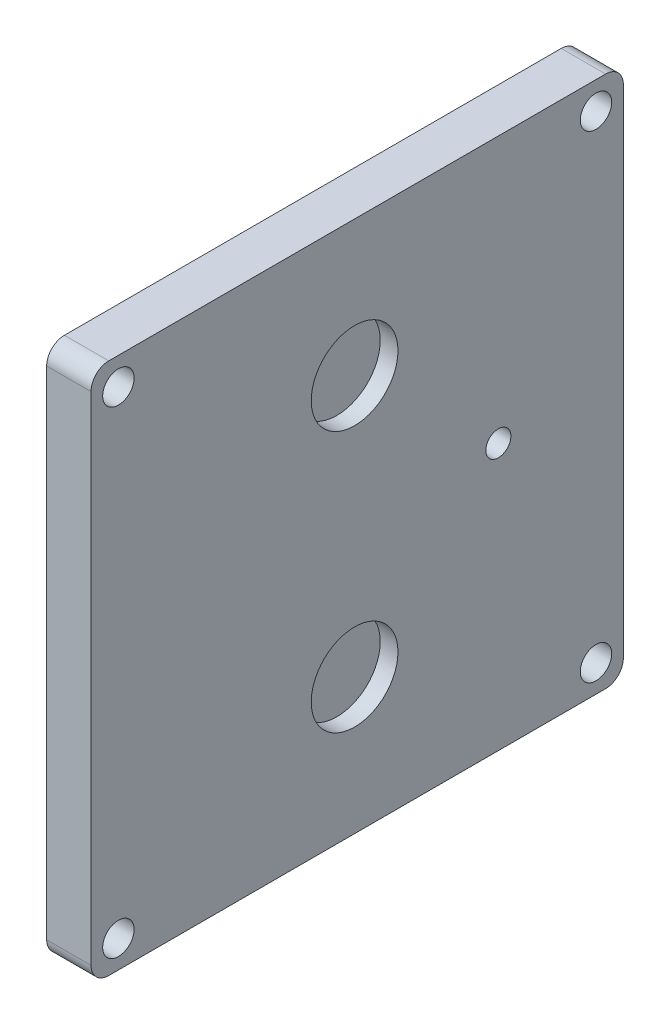
SolidWorks part; units mm, degrees
ref_plane "Front Plane" through (0, 0, 0) normal (0, 0, 1) x (1, 0, 0)
ref_plane "Top Plane" through (0, 0, 0) normal (0, 1, 0) x (1, 0, 0)
ref_plane "Right Plane" through (0, 0, 0) normal (1, 0, 0) x (0, 0, -1)
sketch "Sketch2" plane through (0, 0, 0) normal (1, 0, 0) x (0, 0, -1)
  line L1 (-35.56, -38.1) -> (35.56, -38.1)
  line L2 (-38.1, -35.56) -> (-38.1, 35.56)
  line L3 (-35.56, 38.1) -> (35.56, 38.1)
  line L4 (38.1, -35.56) -> (38.1, 35.56)
  line L5 (-38.1, -38.1) -> (38.1, 38.1) construction
  line L6 (-38.1, 38.1) -> (38.1, -38.1) construction
  arc A0 (-35.56, -38.1) -> (-38.1, -35.56) centre (-35.56, -35.56) cw
  arc A1 (35.56, -38.1) -> (38.1, -35.56) centre (35.56, -35.56) ccw
  arc A2 (35.56, 38.1) -> (38.1, 35.56) centre (35.56, 35.56) cw
  arc A3 (-38.1, 35.56) -> (-35.56, 38.1) centre (-35.56, 35.56) cw
  point P0 (0, 0)
  dimension "D3" = 2.54
  dimension "D1" = 76.2
  dimension "D2" = 76.2
extrude "Boss-Extrude1" add sketch "Sketch2" along normal blind 6.35
sketch "Sketch3" plane through (6.35, 0, 0) normal (1, 0, 0) x (0, 0, -1)
  line L0 (0, 38.1) -> (0, -38.1) construction
  line L1 (35.56, 38.1) -> (-35.56, 38.1) construction
  line L2 (-35.56, -38.1) -> (35.56, -38.1) construction
  line L3 (38.1, 0) -> (-38.1, 0) construction
  line L4 (38.1, -35.56) -> (38.1, 35.56) construction
  line L5 (-38.1, 35.56) -> (-38.1, -35.56) construction
  line L6 (-38.1, 0) -> (37.3561, 37.3561) construction
  line L7 (-38.1, 0) -> (37.3561, -37.3561) construction
  arc A0 (38.1, 35.56) -> (35.56, 38.1) centre (35.56, 35.56) ccw construction
  arc A1 (35.56, -38.1) -> (38.1, -35.56) centre (35.56, -35.56) ccw construction
  circle A2 centre (-0.372, -18.678) radius 6.21
  circle A3 centre (-0.372, 18.678) radius 6.21
  dimension "D1" = 12.42
  dimension "D2" = 12.42
sketch "Sketch6" plane through (6.35, 0, 0) normal (1, 0, 0) x (0, 0, -1)
  line L0 (38.1, 0) -> (-38.1, 0) construction
  circle A0 centre (20.2063, 0) radius 1.778
extrude "Cut-Extrude1" cut sketch "Sketch6" against normal through all
sketch "Sketch14" plane through (6.35, 0, 0) normal (1, 0, 0) x (0, 0, -1)
extrude "Cut-Extrude5" cut sketch "Sketch3" against normal blind 2.54 contours A2 | A3
sketch "Sketch16" plane through (6.35, 0, 0) normal (1, 0, 0) x (0, 0, -1)
  circle A0 centre (20.2063, 0) radius 1.778
sketch "Sketch17" plane through (0, 0, 0) normal (-1, 0, 0) x (0, 0, 1)
  line L6 (-31.75, -31.75) -> (31.75, -31.75)
  line L7 (-31.75, -31.75) -> (-31.75, 31.75)
  line L11 (-31.75, 31.75) -> (31.75, 31.75)
  line L12 (31.75, -31.75) -> (31.75, 31.75)
  line L13 (-31.75, -31.75) -> (31.75, 31.75) construction
  line L14 (-31.75, 31.75) -> (31.75, -31.75) construction
  point P0 (0, 0)
  point P1 (0, 0)
extrude "Boss-Extrude2" add sketch "Sketch17" along normal blind 2.54
fillet "Fillet1" radius 2.54 4 edges at (-1.27, -31.75, 31.75) (-1.27, -31.75, -31.75) (-1.27, 31.75, -31.75) (-1.27, 31.75, 31.75)
sketch "Sketch18" plane through (-2.54, 0, 0) normal (-1, 0, 0) x (0, 0, 1)
  circle A0 centre (-20.2063, 0) radius 1.7965
extrude "Cut-Extrude6" cut sketch "Sketch18" against normal through all
sketch "Sketch21" plane through (-2.54, 0, 0) normal (-1, 0, 0) x (0, 0, 1)
  line L0 (-34.1811, 34.1811) -> (-34.1811, -34.1811) construction
  line L1 (-34.1811, -34.1811) -> (34.1811, -34.1811) construction
  line L2 (31.0061, 31.0061) -> (37.3561, 37.3561) construction
  line L3 (-31.0061, 31.0061) -> (-37.3561, 37.3561) construction
  line L4 (31.0061, -31.0061) -> (37.3561, -37.3561) construction
  line L5 (-31.0061, -31.0061) -> (-37.3561, -37.3561) construction
  line L6 (34.1811, -34.1811) -> (34.1811, 34.1811) construction
  line L7 (34.1811, 34.1811) -> (-34.1811, 34.1811) construction
  arc A0 (-35.56, 38.1) -> (-38.1, 35.56) centre (-35.56, 35.56) ccw construction
  arc A1 (35.56, -38.1) -> (38.1, -35.56) centre (35.56, -35.56) ccw construction
  arc A2 (-38.1, -35.56) -> (-35.56, -38.1) centre (-35.56, -35.56) ccw construction
  arc A3 (38.1, 35.56) -> (35.56, 38.1) centre (35.56, 35.56) ccw construction
  arc A4 (31.75, 29.21) -> (29.21, 31.75) centre (29.21, 29.21) ccw construction
  arc A5 (-29.21, 31.75) -> (-31.75, 29.21) centre (-29.21, 29.21) ccw construction
  arc A6 (-31.75, -29.21) -> (-29.21, -31.75) centre (-29.21, -29.21) ccw construction
sketch "Sketch22" plane through (0, 0, 0) normal (-1, 0, 0) x (0, 0, 1)
  point P0 (-34.1811, 34.1811)
  point P3 (34.1811, 34.1811)
  point P6 (34.1811, -34.1811)
  point P9 (-34.1811, -34.1811)
hole_wizard "M4 Clearance Hole1" positions "Sketch22" profile "Sketch23" hole size "M4" standard "ANSI Metric"
sketch "Sketch23" plane through (0, 34.1811, -34.1811) normal (0, 1, 0) x (0, 0, 1)
  line L0 (0, 0) -> (0, 15.3219)
  line L1 (0, 15.3219) -> (2.25, 13.97)
  line L2 (2.25, 13.97) -> (2.25, 0)
  line L5 (2.25, 0) -> (0, 0)
  line L10 (0, 15.3219) -> (-2.25, 13.97) construction
  line L11 (0, -6.35) -> (0, 107.95) construction
  dimension "Hole Dia." = 4.5
  dimension "Hole Depth" = 13.97
  dimension "Drill Angle" = 118
sketch "Sketch24" plane through (-2.54, 0, 0) normal (-1, 0, 0) x (0, 0, 1)
  line L3 (-25.4, -29.845) -> (25.4, -29.845)
  line L4 (-25.4, -29.845) -> (-25.4, -26.035)
  line L5 (-25.4, -26.035) -> (25.4, -26.035)
  line L6 (25.4, -29.845) -> (25.4, -26.035)
  line L7 (-25.4, -29.845) -> (25.4, -26.035) construction
  line L8 (-25.4, -26.035) -> (25.4, -29.845) construction
  line L10 (-25.4, 29.845) -> (25.4, 29.845)
  line L11 (-25.4, 29.845) -> (-25.4, 26.035)
  line L12 (-25.4, 26.035) -> (25.4, 26.035)
  line L13 (25.4, 29.845) -> (25.4, 26.035)
  line L14 (-25.4, 29.845) -> (25.4, 26.035) construction
  line L15 (-25.4, 26.035) -> (25.4, 29.845) construction
  dimension "D2" = 50.8
  dimension "D3" = 3.81
  dimension "D4" = 50.8
  dimension "D5" = 3.81
extrude "Cut-Extrude7" cut sketch "Sketch24" against normal blind 5.08
fillet "Fillet3" radius 1.27 8 edges at (0, 29.845, -25.4) (0, 29.845, 25.4) (0, 26.035, 25.4) (0, 26.035, -25.4) (0, -29.845, -25.4) (0, -26.035, 25.4) (0, -29.845, 25.4) (0, -26.035, -25.4)
